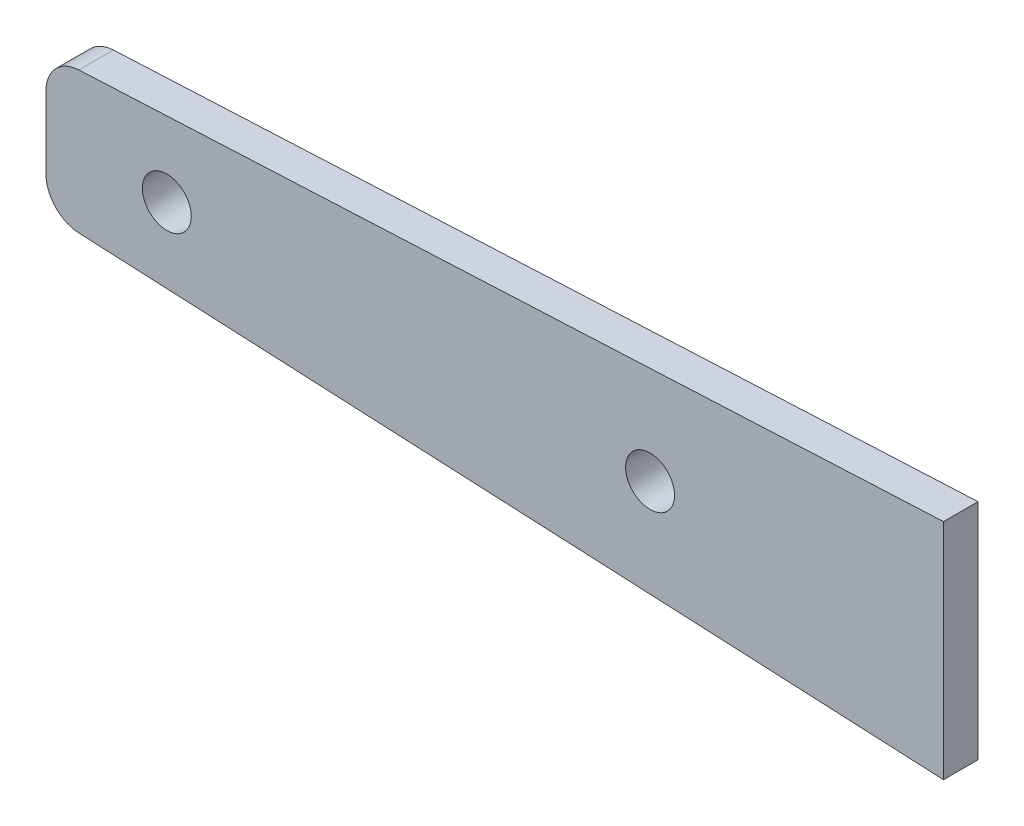
SolidWorks part; units mm, degrees
material "ASTM A36 Steel"
ref_plane "X-Y Datum" through (0, 0, 0) normal (0, 0, 1) x (1, 0, 0)
ref_plane "X-Z Datum" through (0, 0, 0) normal (0, 1, 0) x (1, 0, 0)
ref_plane "Y-Z Datum" through (0, 0, 0) normal (1, 0, 0) x (0, 0, -1)
sketch "Sketch1" plane through (0, 0, 0) normal (0, 0, 1) x (1, 0, 0)
  line L0 (-22.225, 0) -> (22.225, 0) construction
  line L1 (33.3375, 9.525) -> (33.3375, -9.525) construction
  line L6 (-33.3375, 9.525) -> (33.3375, 9.525) construction
  line L7 (-33.3375, 9.525) -> (-33.3375, -9.525) construction
  line L12 (-33.3375, -9.525) -> (33.3375, -9.525) construction
  line L13 (33.3375, 9.525) -> (33.3375, -9.525) construction
  line L14 (-33.3375, 9.525) -> (33.3375, -9.525) construction
  line L15 (-33.3375, -9.525) -> (33.3375, 9.525) construction
  line L16 (-33.3375, 6.35) -> (-33.3375, -6.35)
  line L17 (-33.3375, 6.35) -> (33.3375, 9.525)
  line L18 (-33.3375, -6.35) -> (33.3375, -9.525)
  line L19 (49.2125, 10.281) -> (49.2125, -10.281)
  line L21 (33.3375, 9.525) -> (33.3375, -9.525) construction
  line L24 (33.3375, 9.525) -> (49.2125, 10.281)
  line L25 (33.3375, -9.525) -> (49.2125, -10.281)
  circle A2 centre (-22.225, 0) radius 2 construction
  circle A3 centre (22.225, 0) radius 2 construction
  point P6 (0, 0)
  point P8 (0, 0)
  point P14 (33.3375, 0)
  point P16 (-33.3375, 0)
  point P19 (49.2125, 0)
  dimension "D1" = 4
  dimension "D2" = 19.05
  dimension "D3" = 66.675
  dimension "D4" = 44.45
  dimension "D5" = 12.7
  dimension "D6" = 15.875
extrude "Boss-Extrude1" add sketch "Sketch1" along normal blind 3.175 contours L12 | L16 L18 L1 L17 | L1 region at (11.1895, 0, 0)
hole_wizard "M4 Clearance Hole2" positions "Sketch9" profile "Sketch8" hole size "M4" standard "ANSI Metric" end condition through all
sketch "Sketch9" plane through (0, 0, 3.175) normal (0, 0, 1) x (1, 0, 0)
  point P0 (-22.225, 0)
  point P3 (22.225, 0)
sketch "Sketch8" plane through (-22.225, 0, 3.175) normal (1, 0, 0) x (0, -1, 0)
  line L0 (0, 0) -> (0, 3.175)
  line L1 (0, 3.175) -> (2.25, 3.175)
  line L2 (2.25, 3.175) -> (2.25, 0)
  line L5 (2.25, 0) -> (0, 0)
  line L11 (0, -6.35) -> (0, 107.95) construction
  dimension "Thru Hole Dia." = 4.5
  dimension "Thru Hole Depth" = 3.175
fillet "Fillet1" radius 3.175 2 edges at (-33.3375, -6.35, 1.5875) (-33.3375, 6.35, 1.5875)
